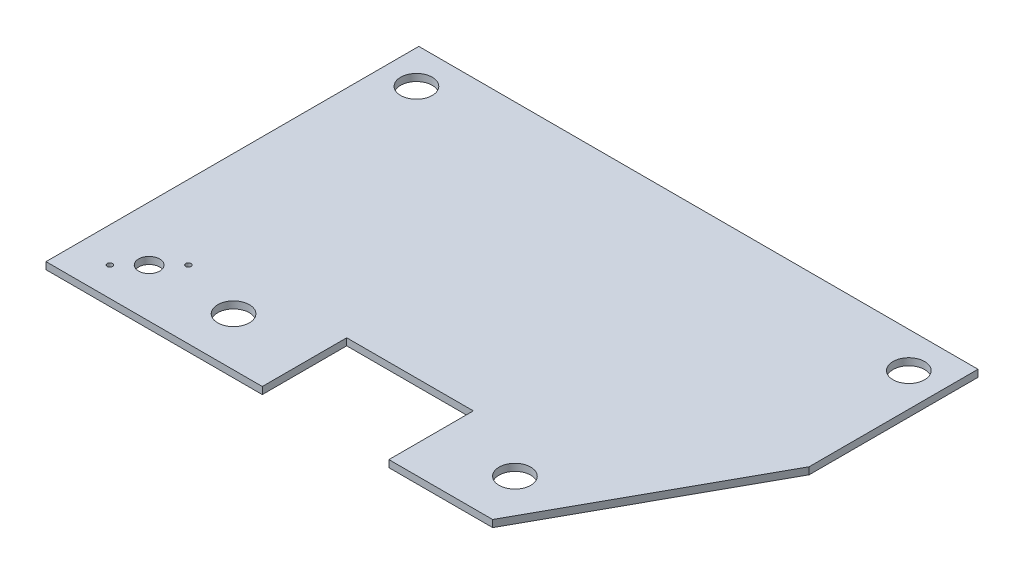
SolidWorks part; units mm, degrees
ref_plane "Front Plane" through (0, 0, 0) normal (0, 0, 1) x (1, 0, 0)
ref_plane "Top Plane" through (0, 0, 0) normal (0, 1, 0) x (1, 0, 0)
ref_plane "Right Plane" through (0, 0, 0) normal (1, 0, 0) x (0, 0, -1)
sketch "Sketch1" plane through (0, 0, 0) normal (0, 1, 0) x (1, 0, 0)
  line L1 (-252.4125, -168.275) -> (252.4125, -168.275)
  line L2 (-252.4125, -168.275) -> (-252.4125, 168.275)
  line L3 (-252.4125, 168.275) -> (252.4125, 168.275)
  line L4 (252.4125, -168.275) -> (252.4125, 168.275)
  line L5 (-252.4125, -168.275) -> (252.4125, 168.275) construction
  line L6 (-252.4125, 168.275) -> (252.4125, -168.275) construction
  point P0 (0, 0)
  dimension "D1" = 504.825
  dimension "D2" = 336.55
extrude "Boss-Extrude1" add sketch "Sketch1" along normal mid plane 6.35
sketch "Sketch2" plane through (0, 3.175, 0) normal (0, 1, 0) x (1, 0, 0)
  line L0 (-222.25, 135.9753) -> (222.25, 135.9753) construction
  line L1 (0, 168.275) -> (0, -168.275) construction
  line L2 (252.4125, 168.275) -> (-252.4125, 168.275) construction
  line L3 (-252.4125, -168.275) -> (252.4125, -168.275) construction
  line L4 (-127, -124.3747) -> (127, -124.3747) construction
  circle A0 centre (-222.25, 135.9753) radius 14.2748
  circle A1 centre (222.25, 135.9753) radius 14.2748
  circle A2 centre (-127, -124.3747) radius 14.2748
  circle A3 centre (127, -124.3747) radius 14.2748
  point P10 (0, 135.9753)
  point P15 (0, -124.3747)
  dimension "D1" = 28.5496
  dimension "D2" = 28.5496
  dimension "D4" = 28.5496
  dimension "D5" = 28.5496
  dimension "D3" = 444.5
  dimension "D6" = 254
  dimension "D7" = 260.35
  dimension "D8" = 32.2997
extrude "Cut-Extrude1" cut sketch "Sketch2" against normal through all
sketch "Sketch5" plane through (0, -3.175, 0) normal (0, -1, 0) x (1, 0, 0)
  line L0 (252.4125, 168.275) -> (252.4125, -15.875)
  line L1 (252.4125, 168.275) -> (252.4125, -168.275) construction
  line L2 (252.4125, -15.875) -> (150.8125, 168.275)
  line L3 (-252.4125, 168.275) -> (252.4125, 168.275) construction
  line L4 (150.8125, 168.275) -> (252.4125, 168.275)
  line L5 (252.4125, -168.275) -> (-252.4125, -168.275) construction
  line L6 (0, -168.275) -> (0, 168.275) construction
  line L7 (-252.4125, -15.875) -> (-150.8125, 168.275)
  line L8 (-252.4125, 168.275) -> (-252.4125, -15.875)
  line L9 (-150.8125, 168.275) -> (-252.4125, 168.275)
  dimension "D1" = 101.6
  dimension "D2" = 152.4
extrude "Cut-Extrude3" cut sketch "Sketch5" against normal through all
sketch "Sketch6" plane through (0, 3.175, 0) normal (0, 1, 0) x (1, 0, 0)
  line L0 (-150.8125, -168.275) -> (150.8125, -168.275) construction
  line L1 (-57.15, -168.275) -> (57.15, -168.275)
  line L2 (-57.15, -168.275) -> (-57.15, -92.075)
  line L3 (-57.15, -92.075) -> (57.15, -92.075)
  line L4 (57.15, -168.275) -> (57.15, -92.075)
  line L5 (0, -168.275) -> (0, -92.075) construction
  point P8 (0, -130.175)
  dimension "D1" = 114.3
  dimension "D2" = 76.2
extrude "Cut-Extrude4" cut sketch "Sketch6" against normal through all
sketch "Sketch7" [suppressed] plane through (0, 3.175, 0) normal (0, 1, 0) x (1, 0, 0)
  line L0 (-150.8125, -168.275) -> (150.8125, -168.275) construction
  line L1 (-98.425, -168.275) -> (98.425, -168.275)
  line L2 (-98.425, -168.275) -> (-98.425, -422.275)
  line L3 (-98.425, -422.275) -> (98.425, -422.275)
  line L4 (98.425, -168.275) -> (98.425, -422.275)
  line L5 (-98.425, -295.275) -> (98.425, -295.275) construction
  point P8 (0, -295.275)
  dimension "D1" = 196.85
  dimension "D2" = 50.8
extrude "Boss-Extrude2" [suppressed] add sketch "Sketch7" against normal blind 6.35
sketch "Sketch8" plane through (0, 0, 0) normal (0, 1, 0) x (1, 0, 0)
  line L0 (-185.4708, -142.1039) -> (-220.9292, -142.1039) construction
  line L1 (-185.4708, -142.1039) -> (-185.4708, -106.6455) construction
  line L2 (-185.4708, -106.6455) -> (-220.9292, -106.6455) construction
  line L3 (-220.9292, -142.1039) -> (-220.9292, -106.6455) construction
  line L4 (-185.4708, -142.1039) -> (-220.9292, -106.6455) construction
  line L5 (-185.4708, -106.6455) -> (-220.9292, -142.1039) construction
  line L6 (-252.4125, 15.875) -> (-252.4125, -168.275)
  line L7 (-252.4125, -168.275) -> (-150.8125, -168.275)
  line L8 (-252.4125, 15.875) -> (-150.8125, -168.275)
  circle A0 centre (-203.2, -124.3747) radius 9.525
  circle A1 centre (-185.4708, -106.6455) radius 2.413
  circle A2 centre (-220.9292, -142.1039) radius 2.413
  circle A3 centre (-127, -124.3747) radius 14.2748 construction
  circle A4 centre (-127, -124.3747) radius 14.2748 construction
  dimension "D1" = 19.05
  dimension "D2" = 4.826
  dimension "D3" = 35.4584
  dimension "D4" = 76.2
extrude "Boss-Extrude3" add sketch "Sketch8" along normal mid plane 6.35 contours A1 L8 L6 L7 A2 A0 | L8 A1 region at (-219.0675, 0, 106.269) region at (-186.1028, 0, 106.9942)
extrude "Cut-Extrude5" cut sketch "Sketch8<3>" against normal through all both and the other way through all contours L8 A1 | L8 A1 region at (-184.2969, 0, 105.9978) region at (-186.1028, 0, 106.9942)
sketch "Sketch8<3>" plane through (0, 0, 0) normal (0, 1, 0) x (1, 0, 0) same geometry as "Sketch8"
equation "\"D2@Sketch2\"=\"D1@Sketch2\""
equation "\"D4@Sketch2\"=\"D1@Sketch2\""
equation "\"D5@Sketch2\"=\"D1@Sketch2\""
